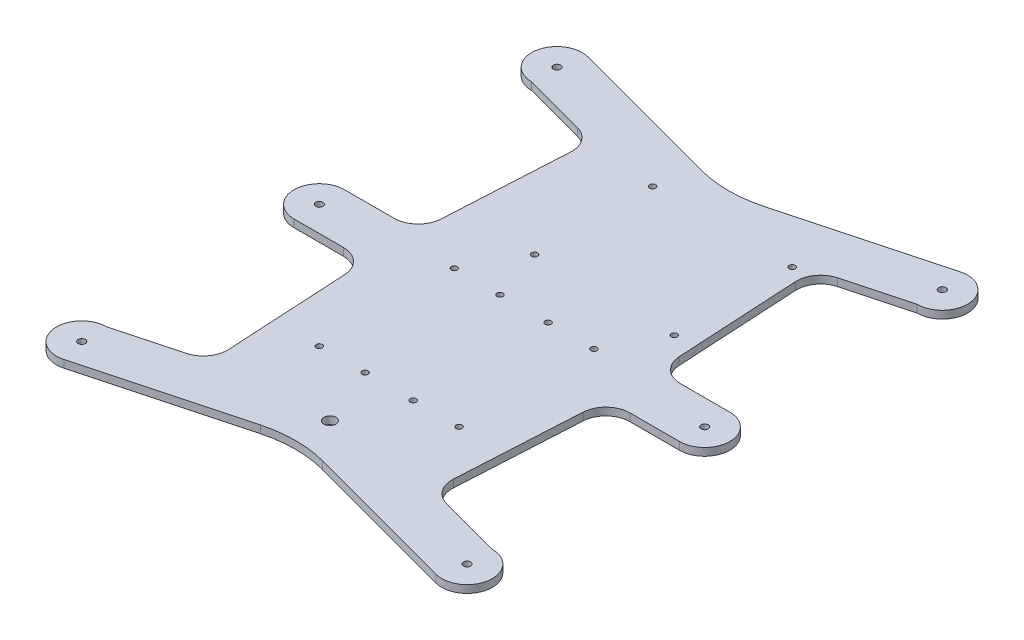
SolidWorks part; units mm, degrees
ref_plane "Front Plane" through (0, 0, 0) normal (0, 0, 1) x (1, 0, 0)
ref_plane "Top Plane" through (0, 0, 0) normal (0, 1, 0) x (1, 0, 0)
ref_plane "Right Plane" through (0, 0, 0) normal (1, 0, 0) x (0, 0, -1)
sketch "Sketch1" plane through (0, 0, 0) normal (0, 1, 0) x (1, 0, 0)
  line L0 (0, 32.1883) -> (0, -21.4181) construction
  line L1 (0, 0) -> (27.1703, 0) construction
  line L2 (-80, 10.5) -> (-50, 10.5)
  line L3 (-50, 10.5) -> (-46.1926, 79.0959)
  line L4 (-46.1926, 79.0959) -> (-80, 88.1546)
  line L5 (-77.2824, 108.7968) -> (0, 88.0891)
  line L6 (77.2824, 108.7968) -> (0, 88.0891)
  line L7 (46.1926, 79.0959) -> (80, 88.1546)
  line L8 (50, 10.5) -> (46.1926, 79.0959)
  line L9 (80, 10.5) -> (50, 10.5)
  line L10 (80, -10.5) -> (50, -10.5)
  line L11 (50, -10.5) -> (46.1926, -79.0959)
  line L12 (46.1926, -79.0959) -> (80, -88.1546)
  line L13 (77.2824, -108.7968) -> (0, -88.0891)
  line L14 (-77.2824, -108.7968) -> (0, -88.0891)
  line L15 (-46.1926, -79.0959) -> (-80, -88.1546)
  line L16 (-50, -10.5) -> (-46.1926, -79.0959)
  line L17 (-80, -10.5) -> (-50, -10.5)
  arc A0 (-80, 10.5) -> (-80, -10.5) centre (-80, 0) ccw
  arc A1 (-77.2824, 108.7968) -> (-80, 88.1546) centre (-80, 98.6546) ccw
  circle A2 centre (-80, 98.6546) radius 1.5
  circle A3 centre (-80, 0) radius 1.5
  circle A4 centre (80, 0) radius 1.5
  circle A5 centre (80, 98.6546) radius 1.5
  arc A6 (77.2824, 108.7968) -> (80, 88.1546) centre (80, 98.6546) cw
  arc A7 (80, 10.5) -> (80, -10.5) centre (80, 0) cw
  arc A8 (77.2824, -108.7968) -> (80, -88.1546) centre (80, -98.6546) ccw
  circle A9 centre (80, -98.6546) radius 1.5
  circle A10 centre (-80, -98.6546) radius 1.5
  arc A11 (-77.2824, -108.7968) -> (-80, -88.1546) centre (-80, -98.6546) cw
  dimension "D2" = 10.5
  dimension "D3" = 3
  dimension "D1" = 75
  dimension "D4" = 80
  dimension "D5" = 30
  dimension "D6" = 35
  dimension "D7" = 68.5959
extrude "Boss-Extrude1" add sketch "Sketch1" along normal blind 3.175
fillet "Fillet1" radius 50 2 edges at (0, 1.5875, -88.0891) (0, 1.5875, 88.0891)
fillet "Fillet2" radius 10 8 edges at (46.1926, 1.5875, 79.0959) (50, 1.5875, 10.5) (50, 1.5875, -10.5) (46.1926, 1.5875, -79.0959) (-46.1926, 1.5875, -79.0959) (-50, 1.5875, -10.5) (-50, 1.5875, 10.5) (-46.1926, 1.5875, 79.0959)
sketch "Sketch2" plane through (0, 3.175, 0) normal (0, 1, 0) x (1, 0, 0)
  line L0 (0, 89.8529) -> (0, -89.8529) construction
  line L1 (10, 5) -> (10, -51) construction
  line L2 (-17.25, 75.619) -> (40.75, 75.619) construction
  line L3 (-17.25, 75.619) -> (-17.25, 26.619) construction
  line L4 (-17.25, 26.619) -> (40.75, 26.619) construction
  line L5 (40.75, 75.619) -> (40.75, 26.619) construction
  line L6 (-17.25, 75.619) -> (-40.75, 75.619) construction
  line L7 (-17.25, 75.619) -> (-17.25, 26.619) construction
  line L8 (-17.25, 26.619) -> (-40.75, 26.619) construction
  line L9 (-40.75, 75.619) -> (-40.75, 26.619) construction
  line L10 (-29, 5) -> (-10, 5) construction
  line L11 (-29, 5) -> (-29, -51) construction
  line L12 (-29, -51) -> (-10, -51) construction
  line L13 (-10, 5) -> (-10, -51) construction
  line L14 (29, -51) -> (10, -51) construction
  line L15 (29, 5) -> (29, -51) construction
  line L16 (29, 5) -> (10, 5) construction
  arc A0 (-12.941, 91.5566) -> (12.941, 91.5566) centre (0, 139.8529) ccw construction
  arc A1 (12.941, -91.5566) -> (-12.941, -91.5566) centre (0, -139.8529) ccw construction
  circle A2 centre (-17.25, 75.619) radius 1.25
  circle A3 centre (40.75, 75.619) radius 1.25
  circle A4 centre (40.75, 26.619) radius 1.25
  circle A5 centre (-17.25, 26.619) radius 1.25
  circle A6 centre (0, -75.6029) radius 2.5
  circle A7 centre (-10, 5) radius 1.25
  circle A8 centre (-10, -51) radius 1.25
  circle A9 centre (-29, 5) radius 1.25
  circle A10 centre (-29, -51) radius 1.25
  circle A11 centre (29, -51) radius 1.25
  circle A12 centre (29, 5) radius 1.25
  circle A13 centre (10, -51) radius 1.25
  circle A14 centre (10, 5) radius 1.25
  dimension "D4" = 2.5
  dimension "D6" = 5
  dimension "D10" = 2.5
  dimension "D1" = 58
  dimension "D2" = 49
  dimension "D3" = 23.5
  dimension "D5" = 40.75
  dimension "D7" = 14.25
  dimension "D8" = 56
  dimension "D9" = 19
  dimension "D11" = 10
  dimension "D12" = 5
extrude "Cut-Extrude1" cut sketch "Sketch2" against normal through all both and the other way through all
